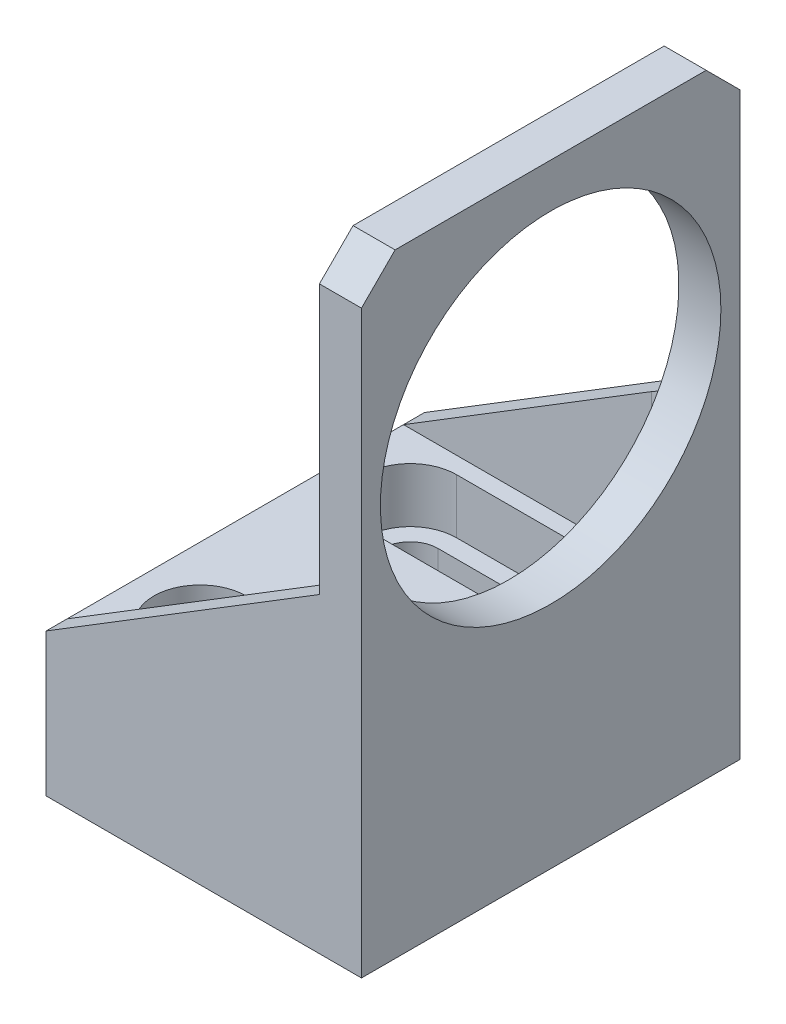
SolidWorks part; units mm, degrees
ref_plane "Front" through (0, 0, 0) normal (0, 0, 1) x (1, 0, 0)
ref_plane "Top" through (0, 0, 0) normal (0, 1, 0) x (1, 0, 0)
ref_plane "Right" through (0, 0, 0) normal (1, 0, 0) x (0, 0, -1)
sketch "Sketch1" plane through (0, 0, 0) normal (1, 0, 0) x (0, 0, -1)
  line L1 (-22.5, 0) -> (22.5, 0)
  line L2 (-22.5, 0) -> (-22.5, 73)
  line L3 (-22.5, 73) -> (22.5, 73)
  line L4 (22.5, 0) -> (22.5, 73)
  circle A0 centre (0, 47.5) radius 20.25
  dimension "D3" = 40.5
  dimension "D1" = 45
  dimension "D2" = 73
  dimension "D4" = 47.5
extrude "Boss-Extrude1" add sketch "Sketch1" along normal blind 5
cosmetic thread "Cosmetic Thread1" parameters "D2"=41
chamfer "Chamfer1" distance 4 angle 45 2 edges at (2.5, 73, -22.5) (2.5, 73, 22.5)
sketch "Sketch2" plane through (0, 0, 0) normal (-1, 0, 0) x (0, 0, 1)
  line L3 (-22.5, 0) -> (-22.5, 17)
  line L4 (-22.5, 0) -> (-22.5, 69) construction
  line L5 (-22.5, 17) -> (22.5, 17)
  line L15 (22.5, 69) -> (22.5, 0) construction
  line L16 (22.5, 17) -> (22.5, 0)
  line L17 (22.5, 0) -> (-22.5, 0)
  dimension "D2" = 17
extrude "Boss-Extrude2" add sketch "Sketch2" along normal blind 32.5 contours L3 L5 L16 L17
hole_wizard "CBORE SLOT for M6 Hex Socket Head Cap Screw1" positions "Sketch3" profile "Sketch4" size "M6" standard "DIN" slot yes end condition up to next
sketch "Sketch3" plane through (0, 17, 0) normal (0, 1, 0) x (1, 0, 0)
  line L0 (-27.5, 12.5) -> (-2.5, 12.5) construction
  line L1 (-32.5, 22.5) -> (-32.5, -22.5) construction
  point P0 (-15, 12.5)
  point P4 (-15, -12.5)
  dimension "D1" = 25
  dimension "D2" = 17.5
  dimension "D3" = 12.5
  dimension "D4" = 12.5
sketch "Sketch4" plane through (-15, 17, -12.5) normal (1, 0, 0) x (0, 0, 1)
  line L0 (0, 0) -> (0, 17)
  line L1 (0, 17) -> (3.3, 17)
  line L3 (3.3, 17) -> (3.3, 6.5)
  line L4 (3.3, 6.5) -> (5.5, 6.5)
  line L5 (5.5, 6.5) -> (5.5, 0)
  line L7 (5.5, 0) -> (0, 0)
  line L11 (0, -6.35) -> (0, 107.95) construction
  dimension "Thru Hole Dia." = 6.6
  dimension "Thru Hole Depth" = 17
  dimension "C'Bore Dia." = 11
  dimension "C'Bore Depth" = 6.5
sketch "Sketch5" plane through (0, 0, 22.5) normal (0, 0, 1) x (1, 0, 0)
  line L0 (0, 37) -> (-32.5, 17)
  line L1 (0, 69) -> (0, 17) construction
  line L2 (-32.5, 17) -> (0, 17)
  line L3 (0, 17) -> (0, 37)
  dimension "D1" = 20
extrude "Boss-Extrude3" add sketch "Sketch5" against normal blind 2.5
fillet "Fillet1" radius 3 1 edges at (0, 27, 20)
mirror "Mirror1" about plane through (0, 0, 0) normal (0, 0, 1) of "Fillet1", "Boss-Extrude3"
